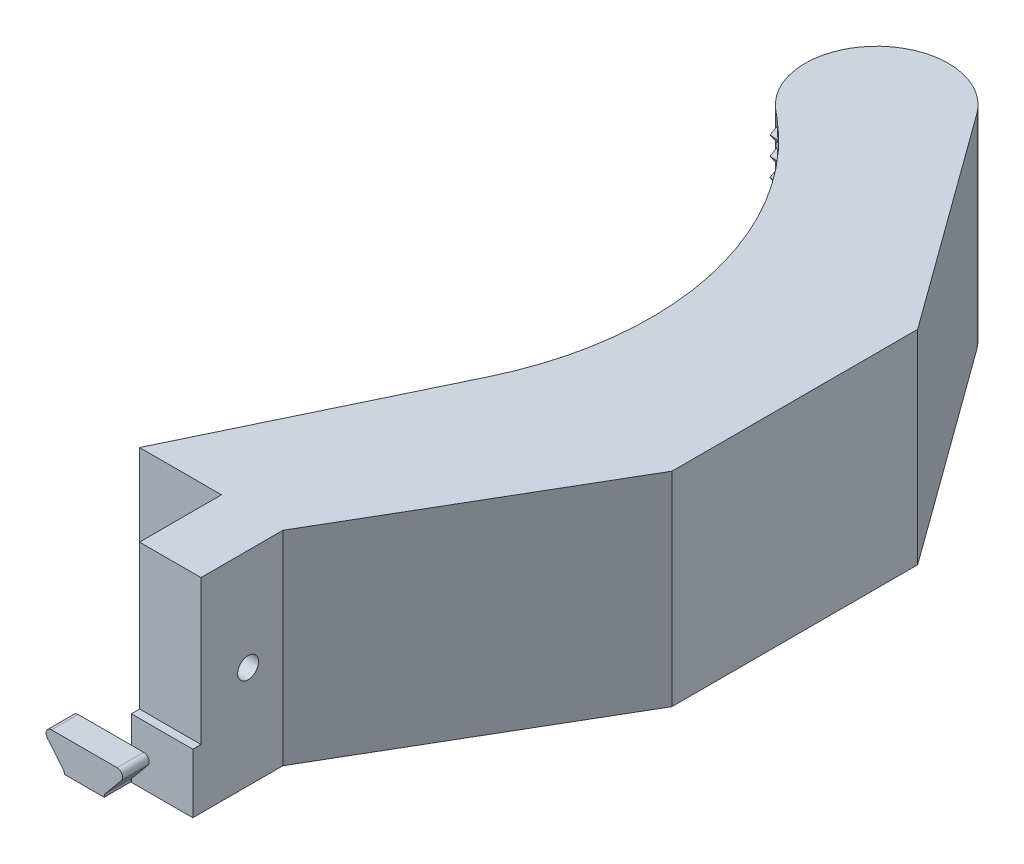
SolidWorks part; units mm, degrees
ref_plane "Front Plane" through (0, 0, 0) normal (0, 0, 1) x (1, 0, 0)
ref_plane "Top Plane" through (0, 0, 0) normal (0, 1, 0) x (1, 0, 0)
ref_plane "Right Plane" through (0, 0, 0) normal (1, 0, 0) x (0, 0, -1)
sketch "Sketch1" plane through (0, 0, 0) normal (0, 0, 1) x (1, 0, 0)
  line L1 (0, 0) -> (-15, 0)
  line L2 (0, 0) -> (0, 14.5)
  line L4 (-15, 0) -> (-15, 14.5)
  line L9 (0, 14.5) -> (-15, 14.5)
  dimension "D2" = 15
  dimension "D3" = 14.5
extrude "Offset" add sketch "Sketch1" along normal blind 2
sketch "Sketch13" plane through (0, 0, 2) normal (0, 0, 1) x (1, 0, 0)
  line L3 (-24.85, 0) -> (-15.15, 0)
  line L6 (-25.2309, 1.0544) -> (-29.0384, 5.6373)
  line L7 (-28, 7.85) -> (-12, 7.85)
  line L8 (-10.9616, 5.6373) -> (-14.7691, 1.0544)
  line L9 (-25.2309, 1.0544) -> (-29.0384, 5.6373)
  line L10 (-28, 7.85) -> (-12, 7.85)
  line L11 (-10.9616, 5.6373) -> (-14.7691, 1.0544)
  arc A8 (-14.7691, 1.0544) -> (-15.15, 0) centre (-13.5, 0) ccw
  arc A9 (-24.85, 0) -> (-25.2309, 1.0544) centre (-26.5, 0) ccw
  arc A10 (-28, 7.85) -> (-29.0384, 5.6373) centre (-28, 6.5) ccw
  arc A11 (-10.9616, 5.6373) -> (-12, 7.85) centre (-12, 6.5) ccw
  arc A12 (-14.7691, 1.0544) -> (-15.15, 0) centre (-13.5, 0) ccw
  arc A13 (-24.85, 0) -> (-25.2309, 1.0544) centre (-26.5, 0) ccw
  arc A14 (-28, 7.85) -> (-29.0384, 5.6373) centre (-28, 6.5) ccw
  arc A15 (-10.9616, 5.6373) -> (-12, 7.85) centre (-12, 6.5) ccw
  dimension "D1" = 0.15
extrude "Dovetail" add sketch "Sketch13" along normal up to surface (6.5 mm away)
sketch "Sketch5" plane through (0, 0, 0) normal (0, 0, -1) x (-1, 0, 0)
  line L0 (15, 14.5) -> (15, 0) construction
  line L1 (0, 0) -> (15, 0)
  line L2 (0, 0) -> (0, 49.8)
  line L3 (0, 49.8) -> (15, 49.8)
  line L4 (15, 0) -> (15, 49.8)
  line L5 (0, 0) -> (15, 49.8) construction
  line L6 (0, 49.8) -> (15, 0) construction
  line L7 (106, 50) -> (-15, 50) construction
  point P4 (7.5, 24.9)
  dimension "D1" = 0.2
extrude "Base" add sketch "Sketch5" along normal blind 20
sketch "Sketch6" plane through (0, 0, 0) normal (0, -1, 0) x (1, 0, 0)
  line L4 (-35, -20) -> (0, -20)
  line L6 (-28.7409, -169.0876) -> (-26.8248, -167.4818)
  line L7 (-7.3824, -77.5523) -> (-35, -20)
  line L9 (0, -20) -> (35, -80)
  line L10 (35, -80) -> (35, -140)
  line L11 (35, -140) -> (-3.341, -192.7846)
  arc A2 (-28.7409, -169.0876) -> (-3.341, -192.7846) centre (-17.5, -182.5) ccw
  arc A3 (-26.8248, -167.4818) -> (-7.3824, -77.5523) centre (-75, -110) ccw
  point P5 (35, -110)
  point P11 (-17.5, -20)
  dimension "D1" = 75
  dimension "D2" = 35
  dimension "D3" = 35
  dimension "D4" = 90
  dimension "D5" = 180
  dimension "D6" = 60
  dimension "D7" = 35
  dimension "D8" = 40
extrude "Gripping" add sketch "Sketch6" against normal up to surface (49.8 mm away) up to face at (-7.5, 49.8, -10)
sketch "Sketch7" plane through (73.5161, 0, -83.3865) normal (-0.6423, 0, 0.7664) x (0.7664, 0, 0.6423)
  line L0 (-132.421, 46.5322) -> (-130.6532, 44.7645)
  line L1 (-132.421, 46.5322) -> (-130.6532, 48.3)
  line L2 (-130.6532, 44.7645) -> (-128.8854, 46.5322)
  line L3 (-130.6532, 48.3) -> (-128.8854, 46.5322)
  line L4 (-27.1253, 49.8) -> (-14.2786, 49.8) construction
  line L5 (-133.421, 49.8) -> (-133.421, 0) construction
  dimension "D1" = 135
  dimension "D2" = 2.5
  dimension "D3" = 1.5
  dimension "D4" = 1
extrude "Texture" add sketch "Sketch7" along normal blind 2 draft 45
pattern_linear "LPattern1" count 1 spacing 4.5 along (-0.7664, 0, -0.6423) count 11 spacing 4.5 along (0, -1, 0) of "Texture"
sketch "Sketch15" plane through (-37.4536, 0, -14.8869) normal (-0.9016, 0, -0.4326) x (-0.4326, 0, 0.9016)
  line L0 (-68.5071, 46.5322) -> (-66.7393, 44.7645)
  line L1 (-68.5071, 46.5322) -> (-66.7393, 48.3)
  line L2 (-66.7393, 44.7645) -> (-64.9716, 46.5322)
  line L3 (-66.7393, 48.3) -> (-64.9716, 46.5322)
  line L6 (-69.5071, 49.8) -> (-5.6714, 49.8) construction
  line L7 (-69.5071, 49.8) -> (-69.5071, 0) construction
  dimension "D1" = 1.5
  dimension "D2" = 2.5
  dimension "D3" = 1
extrude "Texture 2" add sketch "Sketch15" along normal blind 2 draft 45
pattern_linear "LPattern2" count 14 spacing 4.5 along (-0.4326, 0, 0.9016) count 11 spacing 4.5 along (0, -1, 0) of "Texture 2"
sketch "Sketch11" plane through (-15, 0, 0) normal (-1, 0, 0) x (0, 0, 1)
  line L1 (13, 50) -> (13, 0) construction
  line L7 (-21, 50) -> (8.5, 50) construction
  line L8 (-21, 0) -> (8.5, 0) construction
  circle A0 centre (-11.5, 25) radius 2.55
  circle A2 centre (-11.5, 25) radius 2.55 construction
  point P6 (13, 25)
  dimension "D1" = 5.1
extrude "ShaftHole" cut sketch "Sketch11" against normal through all both and the other way through all
